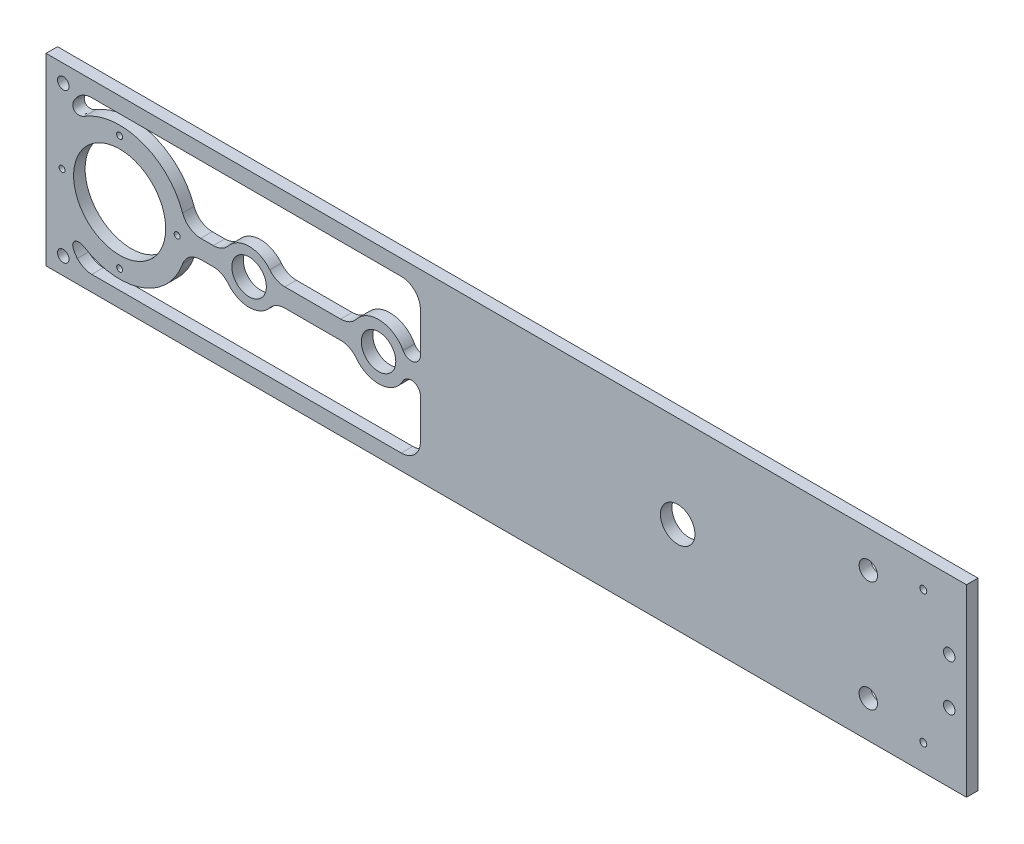
SolidWorks part; units mm, degrees
material "1060 Alloy"
ref_plane "Front Plane" through (0, 0, 0) normal (0, 0, 1) x (1, 0, 0)
ref_plane "Top Plane" through (0, 0, 0) normal (0, 1, 0) x (1, 0, 0)
ref_plane "Right Plane" through (0, 0, 0) normal (1, 0, 0) x (0, 0, -1)
sketch "Sketch1" plane through (0, 0, 0) normal (0, 0, 1) x (1, 0, 0)
  line L1 (0, 50.8) -> (508, 50.8)
  line L2 (0, 50.8) -> (0, -50.8)
  line L3 (0, -50.8) -> (508, -50.8)
  line L4 (508, 50.8) -> (508, -50.8)
  dimension "D1" = 508
  dimension "D2" = 101.6
extrude "Boss-Extrude1" add sketch "Sketch1" against normal blind 6.35
sketch "Sketch2" plane through (0, 0, 0) normal (0, 0, 1) x (1, 0, 0)
  line L0 (0, 50.8) -> (0, -50.8) construction
  circle A0 centre (40.64, 0) radius 25.4
  circle A1 centre (72.39, 0) radius 1.651
  circle A2 centre (40.64, -31.75) radius 1.651
  circle A3 centre (8.89, 0) radius 1.651
  circle A4 centre (40.64, 31.75) radius 1.651
  point P15 (40.64, 0)
  dimension "D1" = 50.8
  dimension "D2" = 3.302
  dimension "D3" = 31.75
  dimension "D4" = 40.64
  dimension "D5" = 4
extrude "Motor mount" cut sketch "Sketch2" against normal blind 6.35
sketch "Sketch3" plane through (0, 0, 0) normal (0, 0, 1) x (1, 0, 0)
  line L0 (398.315, 0) -> (50398.315, 0) construction
  circle A0 centre (40.64, 0) radius 25.4 construction
  circle A1 centre (40.64, 0) radius 25.4 construction
  circle A2 centre (112.0775, 0) radius 9.525
  circle A3 centre (183.515, 0) radius 9.525
  circle A4 centre (348.615, 0) radius 9.525
  circle A5 centre (453.8064, -30.5822) radius 47.9695 construction
  circle A6 centre (484.1695, -36.5735) radius 93.3199 construction
  circle A7 centre (453.8064, -30.5822) radius 47.9695 construction
  circle A8 centre (484.1695, -36.5735) radius 93.3199 construction
  circle A9 centre (453.8064, -30.5822) radius 5.08
  circle A10 centre (484.1695, -36.5735) radius 1.905
  circle A11 centre (484.1695, 36.5735) radius 1.905
  circle A12 centre (453.8064, 30.5822) radius 5.08
  dimension "D1" = 19.05
  dimension "D2" = 19.05
  dimension "D5" = 19.05
  dimension "D7" = 3.81
  dimension "D8" = 10.16
  dimension "D3" = 71.4375
  dimension "D4" = 71.4375
  dimension "D6" = 165.1
extrude "Cut-Extrude2" cut sketch "Sketch3" against normal through all
sketch "Sketch4" plane through (0, 0, 0) normal (0, 0, 1) x (1, 0, 0)
  line L0 (508, 50.8) -> (0, 50.8) construction
  line L1 (0, 50.8) -> (0, -50.8) construction
  line L2 (508, -50.8) -> (508, 50.8) construction
  line L3 (0, -50.8) -> (508, -50.8) construction
  circle A0 centre (9.525, 41.275) radius 3.175
  circle A1 centre (9.525, -41.275) radius 3.175
  circle A2 centre (498.475, 12.7) radius 3.175
  circle A3 centre (498.475, -12.7) radius 3.175
  dimension "D1" = 6.35
  dimension "D2" = 6.35
  dimension "D3" = 6.35
  dimension "D4" = 6.35
  dimension "D5" = 9.525
  dimension "D6" = 9.525
  dimension "D7" = 9.525
  dimension "D8" = 38.1
  dimension "D9" = 9.525
  dimension "D10" = 38.1
extrude "Cut-Extrude3" cut sketch "Sketch4" against normal through all
sketch "Sketch7" plane through (0, 0, 0) normal (0, 0, 1) x (1, 0, 0)
  line L3 (211.7063, 0) -> (211.7063, 47.2876) construction
  line L5 (211.7063, 47.2876) -> (0, 47.2876) construction
  line L6 (0, 47.2876) -> (0, 0) construction
  line L7 (0, 0) -> (40.64, 0) construction
  line L8 (40.64, -5.08) -> (112.0775, -5.08)
  line L9 (112.0775, -5.08) -> (183.515, -5.08)
  line L10 (183.515, -5.08) -> (216.7863, -5.08)
  line L11 (216.7863, -5.08) -> (216.7863, 52.3676)
  line L12 (216.7863, 52.3676) -> (-5.08, 52.3676)
  line L13 (-5.08, 52.3676) -> (-5.08, -5.08)
  line L14 (-5.08, -5.08) -> (40.64, -5.08)
  line L15 (85.4063, 5.08) -> (92.3414, 5.08)
  line L16 (131.8136, 5.08) -> (162.5851, 5.08)
  line L18 (206.6263, 9.6628) -> (206.6263, 31.6032)
  line L19 (196.0219, 42.2076) -> (25.2631, 42.2076)
  line L20 (0, 50.8) -> (0, -50.8) construction
  line L22 (206.6263, 5.08) -> (206.6263, 42.2076) construction
  line L23 (112.0775, 5.08) -> (183.515, 5.08) construction
  line L24 (40.64, 5.08) -> (112.0775, 5.08) construction
  line L25 (206.6263, 42.2076) -> (5.08, 42.2076) construction
  line L26 (5.08, 42.2076) -> (5.08, 5.08) construction
  line L27 (112.0775, 0) -> (183.515, 0) construction
  line L28 (40.64, 0) -> (112.0775, 0) construction
  line L29 (183.515, 0) -> (211.7063, 0) construction
  line L30 (5.08, 5.08) -> (40.64, 5.08) construction
  line L31 (183.515, 5.08) -> (206.6263, 5.08) construction
  circle A0 centre (40.64, 0) radius 31.75 construction
  circle A1 centre (112.0775, 0) radius 9.525
  circle A2 centre (183.515, 0) radius 9.525
  circle A3 centre (9.525, 41.275) radius 3.1307
  arc A4 (100.6434, 9.0867) -> (92.3414, 5.08) centre (92.3414, 15.6844) cw
  arc A5 (197.0687, 7.2633) -> (206.6263, 9.6628) centre (201.5463, 9.6628) ccw
  arc A6 (17.2833, 38.5871) -> (25.2631, 42.2076) centre (25.2631, 31.6032) cw
  arc A7 (206.6263, 31.6032) -> (196.0219, 42.2076) centre (196.0219, 31.6032) ccw
  circle A8 centre (112.0775, 0) radius 4.445
  circle A9 centre (183.515, 0) radius 4.445
  circle A10 centre (40.64, 0) radius 26.67
  arc A11 (197.0687, 7.2633) -> (171.333, 9.3838) centre (183.515, 0) ccw
  arc A12 (162.5851, 5.08) -> (171.333, 9.3838) centre (162.5851, 16.1223) ccw
  arc A13 (123.5116, 9.0867) -> (100.6434, 9.0867) centre (112.0775, 0) ccw
  arc A14 (131.8136, 5.08) -> (123.5116, 9.0867) centre (131.8136, 15.6844) cw
  arc A15 (75.3984, 12.178) -> (21.2634, 31.3209) centre (40.64, 0) ccw
  arc A17 (75.3984, 12.178) -> (85.4063, 5.08) centre (85.4063, 15.6844) ccw
  spline S0 degree 3 poles (17.2833, 38.5871) (11.5305, 32.014) (16.7871, 28.5516) (21.2634, 31.3209) knots 0 0 0 0 1 1 1 1
  dimension "D1" = 5.08
  dimension "D3" = 5.08
  dimension "D4" = 11.0423
  dimension "D5" = 10.6044
  dimension "D6" = 10.6044
  dimension "D7" = 10.6044
  dimension "D2" = 5.08
extrude "Cut-Extrude4" cut sketch "Sketch7" against normal through all contours L19 A6 S0 A15 A17 L15 A4 A13 A14 L16 A12 A11 A5 L18 A7
mirror "Mirror1" about plane through (0, 0, 0) normal (0, 1, 0) of "Cut-Extrude4"
